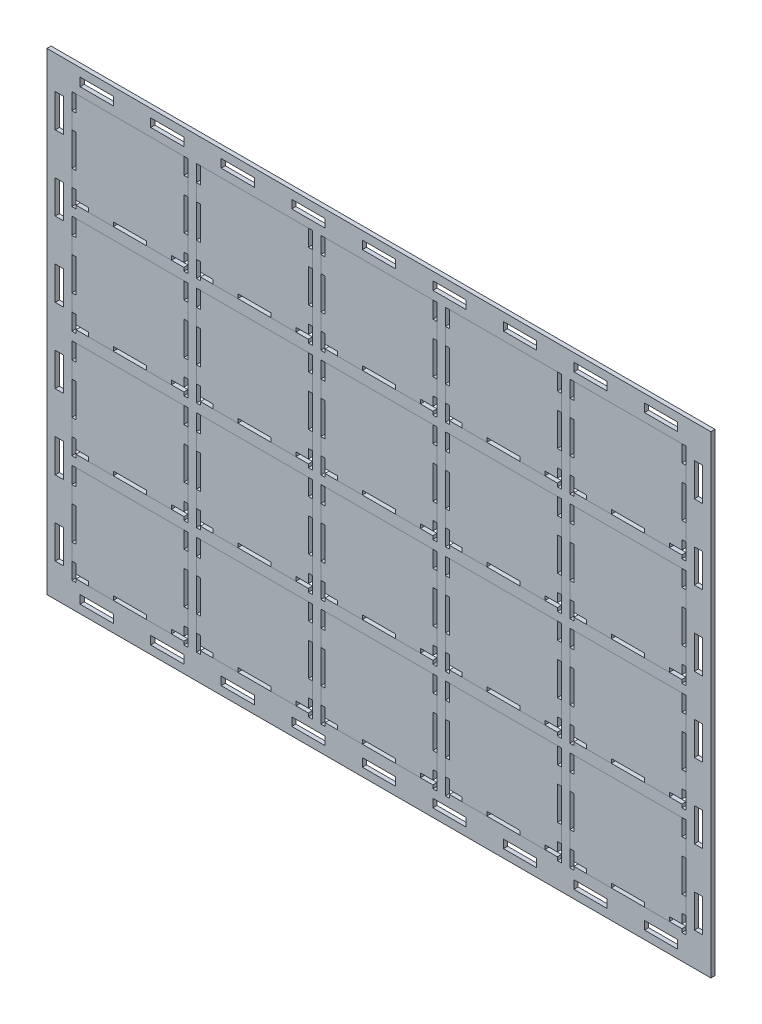
SolidWorks part; units mm, degrees
ref_plane "Front" through (0, 0, 0) normal (0, 0, 1) x (1, 0, 0)
ref_plane "Top" through (0, 0, 0) normal (0, 1, 0) x (1, 0, 0)
ref_plane "Right" through (0, 0, 0) normal (1, 0, 0) x (0, 0, -1)
sketch "Sketch1" plane through (0, 0, 0) normal (0, 0, 1) x (1, 0, 0)
  line L0 (-336.296, -110.6441) -> (-336.296, 164.3559) construction
  line L1 (-341.296, -115.6441) -> (58.704, -115.6441)
  line L2 (-341.296, -115.6441) -> (-341.296, 169.3559)
  line L3 (-341.296, 169.3559) -> (58.704, 169.3559)
  line L4 (58.704, -115.6441) -> (58.704, 169.3559)
  line L5 (-341.296, -115.6441) -> (58.704, 169.3559) construction
  line L6 (-341.296, 169.3559) -> (58.704, -115.6441) construction
  line L7 (-336.296, 164.3559) -> (53.704, 164.3559) construction
  line L8 (53.704, -110.6441) -> (53.704, 164.3559) construction
  line L9 (-336.296, -110.6441) -> (53.704, -110.6441) construction
  line L10 (-331.296, -105.6441) -> (-331.296, 159.3559) construction
  line L11 (-331.296, 159.3559) -> (48.704, 159.3559) construction
  line L12 (48.704, -105.6441) -> (48.704, 159.3559) construction
  line L13 (-331.296, -105.6441) -> (48.704, -105.6441) construction
  line L14 (-26.296, 96.3559) -> (43.704, 96.3559) construction
  line L15 (-26.296, 94.3559) -> (43.704, 94.3559) construction
  line L16 (-26.296, 94.3559) -> (-26.296, 154.3559) construction
  line L17 (-26.296, 154.3559) -> (43.704, 154.3559) construction
  line L18 (43.704, 94.3559) -> (43.704, 154.3559) construction
  line L19 (-26.296, 94.3559) -> (43.704, 154.3559) construction
  line L20 (-26.296, 154.3559) -> (43.704, 94.3559) construction
  line L21 (41.204, 154.3559) -> (41.204, 94.3559) construction
  line L22 (8.704, 134.2642) -> (8.704, 116.5512) construction
  line L23 (-23.796, 154.3559) -> (-23.796, 94.3559) construction
  line L24 (-26.296, 94.3559) -> (-26.296, 154.3559)
  line L25 (-26.296, 154.3559) -> (43.704, 154.3559)
  line L26 (43.704, 154.3559) -> (43.704, 94.3559)
  line L27 (43.704, 94.3559) -> (41.204, 94.3559)
  line L28 (41.204, 94.3559) -> (41.204, 96.3559)
  line L29 (-23.796, 94.3559) -> (-23.796, 96.3559)
  line L30 (-23.796, 96.3559) -> (41.204, 96.3559)
  line L31 (-23.796, 94.3559) -> (-26.296, 94.3559)
  line L32 (-23.796, 29.3559) -> (-26.296, 29.3559)
  line L33 (-26.296, 29.3559) -> (-26.296, 89.3559)
  line L34 (-26.296, 89.3559) -> (43.704, 89.3559)
  line L35 (43.704, 89.3559) -> (43.704, 29.3559)
  line L36 (43.704, 29.3559) -> (41.204, 29.3559)
  line L37 (41.204, 29.3559) -> (41.204, 31.3559)
  line L38 (-23.796, 31.3559) -> (41.204, 31.3559)
  line L39 (-23.796, 29.3559) -> (-23.796, 31.3559)
  line L40 (-23.796, -35.6441) -> (-26.296, -35.6441)
  line L41 (-26.296, -35.6441) -> (-26.296, 24.3559)
  line L42 (-26.296, 24.3559) -> (43.704, 24.3559)
  line L43 (43.704, 24.3559) -> (43.704, -35.6441)
  line L44 (43.704, -35.6441) -> (41.204, -35.6441)
  line L45 (41.204, -35.6441) -> (41.204, -33.6441)
  line L46 (-23.796, -33.6441) -> (41.204, -33.6441)
  line L47 (-23.796, -35.6441) -> (-23.796, -33.6441)
  line L48 (-23.796, -100.6441) -> (-26.296, -100.6441)
  line L49 (-26.296, -100.6441) -> (-26.296, -40.6441)
  line L50 (-26.296, -40.6441) -> (43.704, -40.6441)
  line L51 (43.704, -40.6441) -> (43.704, -100.6441)
  line L52 (43.704, -100.6441) -> (41.204, -100.6441)
  line L53 (41.204, -100.6441) -> (41.204, -98.6441)
  line L54 (-23.796, -98.6441) -> (41.204, -98.6441)
  line L55 (-23.796, -100.6441) -> (-23.796, -98.6441)
  line L56 (-98.796, 94.3559) -> (-101.296, 94.3559)
  line L57 (-101.296, 94.3559) -> (-101.296, 154.3559)
  line L58 (-101.296, 154.3559) -> (-31.296, 154.3559)
  line L59 (-31.296, 154.3559) -> (-31.296, 94.3559)
  line L60 (-31.296, 94.3559) -> (-33.796, 94.3559)
  line L61 (-33.796, 94.3559) -> (-33.796, 96.3559)
  line L62 (-98.796, 96.3559) -> (-33.796, 96.3559)
  line L63 (-98.796, 94.3559) -> (-98.796, 96.3559)
  line L64 (-98.796, 29.3559) -> (-101.296, 29.3559)
  line L65 (-101.296, 29.3559) -> (-101.296, 89.3559)
  line L66 (-101.296, 89.3559) -> (-31.296, 89.3559)
  line L67 (-31.296, 89.3559) -> (-31.296, 29.3559)
  line L68 (-31.296, 29.3559) -> (-33.796, 29.3559)
  line L69 (-33.796, 29.3559) -> (-33.796, 31.3559)
  line L70 (-98.796, 31.3559) -> (-33.796, 31.3559)
  line L71 (-98.796, 29.3559) -> (-98.796, 31.3559)
  line L72 (-98.796, -35.6441) -> (-101.296, -35.6441)
  line L73 (-101.296, -35.6441) -> (-101.296, 24.3559)
  line L74 (-101.296, 24.3559) -> (-31.296, 24.3559)
  line L75 (-31.296, 24.3559) -> (-31.296, -35.6441)
  line L76 (-31.296, -35.6441) -> (-33.796, -35.6441)
  line L77 (-33.796, -35.6441) -> (-33.796, -33.6441)
  line L78 (-98.796, -33.6441) -> (-33.796, -33.6441)
  line L79 (-98.796, -35.6441) -> (-98.796, -33.6441)
  line L80 (-98.796, -100.6441) -> (-101.296, -100.6441)
  line L81 (-101.296, -100.6441) -> (-101.296, -40.6441)
  line L82 (-101.296, -40.6441) -> (-31.296, -40.6441)
  line L83 (-31.296, -40.6441) -> (-31.296, -100.6441)
  line L84 (-31.296, -100.6441) -> (-33.796, -100.6441)
  line L85 (-33.796, -100.6441) -> (-33.796, -98.6441)
  line L86 (-98.796, -98.6441) -> (-33.796, -98.6441)
  line L87 (-98.796, -100.6441) -> (-98.796, -98.6441)
  line L88 (-173.796, 94.3559) -> (-176.296, 94.3559)
  line L89 (-176.296, 94.3559) -> (-176.296, 154.3559)
  line L90 (-176.296, 154.3559) -> (-106.296, 154.3559)
  line L91 (-106.296, 154.3559) -> (-106.296, 94.3559)
  line L92 (-106.296, 94.3559) -> (-108.796, 94.3559)
  line L93 (-108.796, 94.3559) -> (-108.796, 96.3559)
  line L94 (-173.796, 96.3559) -> (-108.796, 96.3559)
  line L95 (-173.796, 94.3559) -> (-173.796, 96.3559)
  line L96 (-173.796, 29.3559) -> (-176.296, 29.3559)
  line L97 (-176.296, 29.3559) -> (-176.296, 89.3559)
  line L98 (-176.296, 89.3559) -> (-106.296, 89.3559)
  line L99 (-106.296, 89.3559) -> (-106.296, 29.3559)
  line L100 (-106.296, 29.3559) -> (-108.796, 29.3559)
  line L101 (-108.796, 29.3559) -> (-108.796, 31.3559)
  line L102 (-173.796, 31.3559) -> (-108.796, 31.3559)
  line L103 (-173.796, 29.3559) -> (-173.796, 31.3559)
  line L104 (-173.796, -35.6441) -> (-176.296, -35.6441)
  line L105 (-176.296, -35.6441) -> (-176.296, 24.3559)
  line L106 (-176.296, 24.3559) -> (-106.296, 24.3559)
  line L107 (-106.296, 24.3559) -> (-106.296, -35.6441)
  line L108 (-106.296, -35.6441) -> (-108.796, -35.6441)
  line L109 (-108.796, -35.6441) -> (-108.796, -33.6441)
  line L110 (-173.796, -33.6441) -> (-108.796, -33.6441)
  line L111 (-173.796, -35.6441) -> (-173.796, -33.6441)
  line L112 (-173.796, -100.6441) -> (-176.296, -100.6441)
  line L113 (-176.296, -100.6441) -> (-176.296, -40.6441)
  line L114 (-176.296, -40.6441) -> (-106.296, -40.6441)
  line L115 (-106.296, -40.6441) -> (-106.296, -100.6441)
  line L116 (-106.296, -100.6441) -> (-108.796, -100.6441)
  line L117 (-108.796, -100.6441) -> (-108.796, -98.6441)
  line L118 (-173.796, -98.6441) -> (-108.796, -98.6441)
  line L119 (-173.796, -100.6441) -> (-173.796, -98.6441)
  line L120 (-248.796, 94.3559) -> (-251.296, 94.3559)
  line L121 (-251.296, 94.3559) -> (-251.296, 154.3559)
  line L122 (-251.296, 154.3559) -> (-181.296, 154.3559)
  line L123 (-181.296, 154.3559) -> (-181.296, 94.3559)
  line L124 (-181.296, 94.3559) -> (-183.796, 94.3559)
  line L125 (-183.796, 94.3559) -> (-183.796, 96.3559)
  line L126 (-248.796, 96.3559) -> (-183.796, 96.3559)
  line L127 (-248.796, 94.3559) -> (-248.796, 96.3559)
  line L128 (-248.796, 29.3559) -> (-251.296, 29.3559)
  line L129 (-251.296, 29.3559) -> (-251.296, 89.3559)
  line L130 (-251.296, 89.3559) -> (-181.296, 89.3559)
  line L131 (-181.296, 89.3559) -> (-181.296, 29.3559)
  line L132 (-181.296, 29.3559) -> (-183.796, 29.3559)
  line L133 (-183.796, 29.3559) -> (-183.796, 31.3559)
  line L134 (-248.796, 31.3559) -> (-183.796, 31.3559)
  line L135 (-248.796, 29.3559) -> (-248.796, 31.3559)
  line L136 (-248.796, -35.6441) -> (-251.296, -35.6441)
  line L137 (-251.296, -35.6441) -> (-251.296, 24.3559)
  line L138 (-251.296, 24.3559) -> (-181.296, 24.3559)
  line L139 (-181.296, 24.3559) -> (-181.296, -35.6441)
  line L140 (-181.296, -35.6441) -> (-183.796, -35.6441)
  line L141 (-183.796, -35.6441) -> (-183.796, -33.6441)
  line L142 (-248.796, -33.6441) -> (-183.796, -33.6441)
  line L143 (-248.796, -35.6441) -> (-248.796, -33.6441)
  line L144 (-248.796, -100.6441) -> (-251.296, -100.6441)
  line L145 (-251.296, -100.6441) -> (-251.296, -40.6441)
  line L146 (-251.296, -40.6441) -> (-181.296, -40.6441)
  line L147 (-181.296, -40.6441) -> (-181.296, -100.6441)
  line L148 (-181.296, -100.6441) -> (-183.796, -100.6441)
  line L149 (-183.796, -100.6441) -> (-183.796, -98.6441)
  line L150 (-248.796, -98.6441) -> (-183.796, -98.6441)
  line L151 (-248.796, -100.6441) -> (-248.796, -98.6441)
  line L152 (-323.796, 94.3559) -> (-326.296, 94.3559)
  line L153 (-326.296, 94.3559) -> (-326.296, 154.3559)
  line L154 (-326.296, 154.3559) -> (-256.296, 154.3559)
  line L155 (-256.296, 154.3559) -> (-256.296, 94.3559)
  line L156 (-256.296, 94.3559) -> (-258.796, 94.3559)
  line L157 (-258.796, 94.3559) -> (-258.796, 96.3559)
  line L158 (-323.796, 96.3559) -> (-258.796, 96.3559)
  line L159 (-323.796, 94.3559) -> (-323.796, 96.3559)
  line L160 (-323.796, 29.3559) -> (-326.296, 29.3559)
  line L161 (-326.296, 29.3559) -> (-326.296, 89.3559)
  line L162 (-326.296, 89.3559) -> (-256.296, 89.3559)
  line L163 (-256.296, 89.3559) -> (-256.296, 29.3559)
  line L164 (-256.296, 29.3559) -> (-258.796, 29.3559)
  line L165 (-258.796, 29.3559) -> (-258.796, 31.3559)
  line L166 (-323.796, 31.3559) -> (-258.796, 31.3559)
  line L167 (-323.796, 29.3559) -> (-323.796, 31.3559)
  line L168 (-323.796, -35.6441) -> (-326.296, -35.6441)
  line L169 (-326.296, -35.6441) -> (-326.296, 24.3559)
  line L170 (-326.296, 24.3559) -> (-256.296, 24.3559)
  line L171 (-256.296, 24.3559) -> (-256.296, -35.6441)
  line L172 (-256.296, -35.6441) -> (-258.796, -35.6441)
  line L173 (-258.796, -35.6441) -> (-258.796, -33.6441)
  line L174 (-323.796, -33.6441) -> (-258.796, -33.6441)
  line L175 (-323.796, -35.6441) -> (-323.796, -33.6441)
  line L176 (-323.796, -100.6441) -> (-326.296, -100.6441)
  line L177 (-326.296, -100.6441) -> (-326.296, -40.6441)
  line L178 (-326.296, -40.6441) -> (-256.296, -40.6441)
  line L179 (-256.296, -40.6441) -> (-256.296, -100.6441)
  line L180 (-256.296, -100.6441) -> (-258.796, -100.6441)
  line L181 (-258.796, -100.6441) -> (-258.796, -98.6441)
  line L182 (-323.796, -98.6441) -> (-258.796, -98.6441)
  line L183 (-323.796, -100.6441) -> (-323.796, -98.6441)
  line L184 (-119.2091, 26.8559) -> (-161.6715, 26.8559) construction
  line L185 (-321.296, 164.3559) -> (-301.296, 164.3559)
  line L186 (-321.296, 164.3559) -> (-321.296, 159.3559)
  line L187 (-321.296, 159.3559) -> (-301.296, 159.3559)
  line L188 (-301.296, 164.3559) -> (-301.296, 159.3559)
  line L189 (-321.296, 164.3559) -> (-301.296, 159.3559) construction
  line L190 (-321.296, 159.3559) -> (-301.296, 164.3559) construction
  line L191 (-141.296, 49.4928) -> (-141.296, 19.2296) construction
  line L192 (-321.296, -105.6441) -> (-301.296, -105.6441)
  line L193 (-301.296, -110.6441) -> (-301.296, -105.6441)
  line L194 (-321.296, -110.6441) -> (-301.296, -110.6441)
  line L195 (-321.296, -110.6441) -> (-321.296, -105.6441)
  line L196 (-278.796, 164.3559) -> (-278.796, 159.3559)
  line L197 (-278.796, 164.3559) -> (-258.796, 164.3559)
  line L198 (-258.796, 164.3559) -> (-258.796, 159.3559)
  line L199 (-278.796, 159.3559) -> (-258.796, 159.3559)
  line L200 (-278.796, -105.6441) -> (-258.796, -105.6441)
  line L201 (-258.796, -110.6441) -> (-258.796, -105.6441)
  line L202 (-278.796, -110.6441) -> (-258.796, -110.6441)
  line L203 (-278.796, -110.6441) -> (-278.796, -105.6441)
  line L204 (-236.296, 164.3559) -> (-236.296, 159.3559)
  line L205 (-236.296, 164.3559) -> (-216.296, 164.3559)
  line L206 (-216.296, 164.3559) -> (-216.296, 159.3559)
  line L207 (-236.296, 159.3559) -> (-216.296, 159.3559)
  line L208 (-236.296, -105.6441) -> (-216.296, -105.6441)
  line L209 (-216.296, -110.6441) -> (-216.296, -105.6441)
  line L210 (-236.296, -110.6441) -> (-216.296, -110.6441)
  line L211 (-236.296, -110.6441) -> (-236.296, -105.6441)
  line L212 (-193.796, 164.3559) -> (-193.796, 159.3559)
  line L213 (-193.796, 164.3559) -> (-173.796, 164.3559)
  line L214 (-173.796, 164.3559) -> (-173.796, 159.3559)
  line L215 (-193.796, 159.3559) -> (-173.796, 159.3559)
  line L216 (-193.796, -105.6441) -> (-173.796, -105.6441)
  line L217 (-173.796, -110.6441) -> (-173.796, -105.6441)
  line L218 (-193.796, -110.6441) -> (-173.796, -110.6441)
  line L219 (-193.796, -110.6441) -> (-193.796, -105.6441)
  line L220 (-151.296, 164.3559) -> (-151.296, 159.3559)
  line L221 (-151.296, 164.3559) -> (-131.296, 164.3559)
  line L222 (-131.296, 164.3559) -> (-131.296, 159.3559)
  line L223 (-151.296, 159.3559) -> (-131.296, 159.3559)
  line L224 (-151.296, -105.6441) -> (-131.296, -105.6441)
  line L225 (-131.296, -110.6441) -> (-131.296, -105.6441)
  line L226 (-151.296, -110.6441) -> (-131.296, -110.6441)
  line L227 (-151.296, -110.6441) -> (-151.296, -105.6441)
  line L228 (-108.796, 164.3559) -> (-108.796, 159.3559)
  line L229 (-108.796, 164.3559) -> (-88.796, 164.3559)
  line L230 (-88.796, 164.3559) -> (-88.796, 159.3559)
  line L231 (-108.796, 159.3559) -> (-88.796, 159.3559)
  line L232 (-108.796, -105.6441) -> (-88.796, -105.6441)
  line L233 (-88.796, -110.6441) -> (-88.796, -105.6441)
  line L234 (-108.796, -110.6441) -> (-88.796, -110.6441)
  line L235 (-108.796, -110.6441) -> (-108.796, -105.6441)
  line L236 (-66.296, 164.3559) -> (-66.296, 159.3559)
  line L237 (-66.296, 164.3559) -> (-46.296, 164.3559)
  line L238 (-46.296, 164.3559) -> (-46.296, 159.3559)
  line L239 (-66.296, 159.3559) -> (-46.296, 159.3559)
  line L240 (-66.296, -105.6441) -> (-46.296, -105.6441)
  line L241 (-46.296, -110.6441) -> (-46.296, -105.6441)
  line L242 (-66.296, -110.6441) -> (-46.296, -110.6441)
  line L243 (-66.296, -110.6441) -> (-66.296, -105.6441)
  line L244 (-23.796, 164.3559) -> (-23.796, 159.3559)
  line L245 (-23.796, 164.3559) -> (-3.796, 164.3559)
  line L246 (-3.796, 164.3559) -> (-3.796, 159.3559)
  line L247 (-23.796, 159.3559) -> (-3.796, 159.3559)
  line L248 (-23.796, -105.6441) -> (-3.796, -105.6441)
  line L249 (-3.796, -110.6441) -> (-3.796, -105.6441)
  line L250 (-23.796, -110.6441) -> (-3.796, -110.6441)
  line L251 (-23.796, -110.6441) -> (-23.796, -105.6441)
  line L252 (18.704, 164.3559) -> (18.704, 159.3559)
  line L253 (18.704, 164.3559) -> (38.704, 164.3559)
  line L254 (38.704, 164.3559) -> (38.704, 159.3559)
  line L255 (18.704, 159.3559) -> (38.704, 159.3559)
  line L256 (18.704, -105.6441) -> (38.704, -105.6441)
  line L257 (38.704, -110.6441) -> (38.704, -105.6441)
  line L258 (18.704, -110.6441) -> (38.704, -110.6441)
  line L259 (18.704, -110.6441) -> (18.704, -105.6441)
  line L260 (48.704, 129.3559) -> (53.704, 129.3559)
  line L261 (-331.296, 149.3559) -> (-336.296, 149.3559)
  line L262 (-331.296, 149.3559) -> (-331.296, 129.3559)
  line L263 (-331.296, 129.3559) -> (-336.296, 129.3559)
  line L264 (-336.296, 149.3559) -> (-336.296, 129.3559)
  line L265 (-331.296, 149.3559) -> (-336.296, 129.3559) construction
  line L266 (-331.296, 129.3559) -> (-336.296, 149.3559) construction
  line L267 (53.704, 149.3559) -> (53.704, 129.3559)
  line L268 (48.704, 149.3559) -> (53.704, 149.3559)
  line L269 (48.704, 149.3559) -> (48.704, 129.3559)
  line L270 (-331.296, 104.3559) -> (-331.296, 84.3559)
  line L271 (-331.296, 104.3559) -> (-336.296, 104.3559)
  line L272 (-336.296, 104.3559) -> (-336.296, 84.3559)
  line L273 (-331.296, 84.3559) -> (-336.296, 84.3559)
  line L274 (48.704, 84.3559) -> (53.704, 84.3559)
  line L275 (53.704, 104.3559) -> (53.704, 84.3559)
  line L276 (48.704, 104.3559) -> (53.704, 104.3559)
  line L277 (48.704, 104.3559) -> (48.704, 84.3559)
  line L278 (-331.296, 59.3559) -> (-331.296, 39.3559)
  line L279 (-331.296, 59.3559) -> (-336.296, 59.3559)
  line L280 (-336.296, 59.3559) -> (-336.296, 39.3559)
  line L281 (-331.296, 39.3559) -> (-336.296, 39.3559)
  line L282 (48.704, 39.3559) -> (53.704, 39.3559)
  line L283 (53.704, 59.3559) -> (53.704, 39.3559)
  line L284 (48.704, 59.3559) -> (53.704, 59.3559)
  line L285 (48.704, 59.3559) -> (48.704, 39.3559)
  line L286 (-331.296, 14.3559) -> (-331.296, -5.6441)
  line L287 (-331.296, 14.3559) -> (-336.296, 14.3559)
  line L288 (-336.296, 14.3559) -> (-336.296, -5.6441)
  line L289 (-331.296, -5.6441) -> (-336.296, -5.6441)
  line L290 (48.704, -5.6441) -> (53.704, -5.6441)
  line L291 (53.704, 14.3559) -> (53.704, -5.6441)
  line L292 (48.704, 14.3559) -> (53.704, 14.3559)
  line L293 (48.704, 14.3559) -> (48.704, -5.6441)
  line L294 (-331.296, -30.6441) -> (-331.296, -50.6441)
  line L295 (-331.296, -30.6441) -> (-336.296, -30.6441)
  line L296 (-336.296, -30.6441) -> (-336.296, -50.6441)
  line L297 (-331.296, -50.6441) -> (-336.296, -50.6441)
  line L298 (48.704, -50.6441) -> (53.704, -50.6441)
  line L299 (53.704, -30.6441) -> (53.704, -50.6441)
  line L300 (48.704, -30.6441) -> (53.704, -30.6441)
  line L301 (48.704, -30.6441) -> (48.704, -50.6441)
  line L302 (-331.296, -75.6441) -> (-331.296, -95.6441)
  line L303 (-331.296, -75.6441) -> (-336.296, -75.6441)
  line L304 (-336.296, -75.6441) -> (-336.296, -95.6441)
  line L305 (-331.296, -95.6441) -> (-336.296, -95.6441)
  line L306 (48.704, -95.6441) -> (53.704, -95.6441)
  line L307 (53.704, -75.6441) -> (53.704, -95.6441)
  line L308 (48.704, -75.6441) -> (53.704, -75.6441)
  line L309 (48.704, -75.6441) -> (48.704, -95.6441)
  line L310 (-26.296, 98.8559) -> (43.704, 98.8559) construction
  line L311 (-26.296, 94.3559) -> (43.704, 94.3559) construction
  line L312 (-26.296, 94.3559) -> (-26.296, 154.3559) construction
  line L313 (-26.296, 154.3559) -> (43.704, 154.3559) construction
  line L314 (43.704, 94.3559) -> (43.704, 154.3559) construction
  line L315 (-26.296, 94.3559) -> (43.704, 154.3559) construction
  line L316 (-26.296, 154.3559) -> (43.704, 94.3559) construction
  line L317 (8.704, 132.327) -> (8.704, 114.7588) construction
  line L318 (-16.296, 124.3559) -> (33.704, 124.3559) construction
  line L319 (-23.796, 154.3559) -> (-23.796, 94.3559) construction
  line L320 (41.204, 154.3559) -> (41.204, 94.3559) construction
  line L321 (33.704, 96.3559) -> (18.704, 96.3559)
  line L322 (-16.296, 98.8559) -> (-1.296, 98.8559) construction
  line L323 (-16.296, 98.8559) -> (-16.296, 96.3559)
  line L324 (-16.296, 96.3559) -> (-1.296, 96.3559)
  line L325 (-1.296, 98.8559) -> (-1.296, 96.3559)
  line L326 (-16.296, 98.8559) -> (-1.296, 96.3559) construction
  line L327 (-16.296, 96.3559) -> (-1.296, 98.8559) construction
  line L328 (18.704, 98.8559) -> (18.704, 96.3559)
  line L329 (33.704, 98.8559) -> (18.704, 98.8559) construction
  line L330 (33.704, 98.8559) -> (33.704, 96.3559)
  line L331 (-23.796, 114.3559) -> (-23.796, 134.3559)
  line L332 (-23.796, 134.3559) -> (-26.296, 134.3559)
  line L333 (-26.296, 134.3559) -> (-26.296, 144.3559)
  line L334 (-26.296, 144.3559) -> (-23.796, 144.3559)
  line L335 (-23.796, 144.3559) -> (-23.796, 154.3559) construction
  line L336 (-23.796, 154.3559) -> (41.204, 154.3559) construction
  line L337 (41.204, 144.3559) -> (41.204, 154.3559) construction
  line L338 (43.704, 144.3559) -> (41.204, 144.3559)
  line L339 (43.704, 134.3559) -> (43.704, 144.3559)
  line L340 (41.204, 134.3559) -> (43.704, 134.3559)
  line L341 (41.204, 114.3559) -> (41.204, 134.3559)
  line L342 (41.204, 114.3559) -> (43.704, 114.3559)
  line L343 (43.704, 114.3559) -> (43.704, 104.3559)
  line L344 (43.704, 104.3559) -> (41.204, 104.3559)
  line L345 (-23.796, 104.3559) -> (-23.796, 98.8559)
  line L346 (-23.796, 98.8559) -> (-16.296, 98.8559)
  line L347 (-26.296, 104.3559) -> (-23.796, 104.3559)
  line L348 (-26.296, 114.3559) -> (-26.296, 104.3559)
  line L349 (-23.796, 114.3559) -> (-26.296, 114.3559)
  line L350 (-23.796, 154.3559) -> (41.204, 154.3559)
  line L351 (-23.796, 154.3559) -> (-23.796, 144.3559)
  line L352 (41.204, 154.3559) -> (41.204, 144.3559)
  line L353 (-1.296, 98.8559) -> (18.704, 98.8559)
  line L354 (33.704, 98.8559) -> (41.204, 98.8559)
  line L355 (41.204, 98.8559) -> (41.204, 104.3559)
  line L356 (-1.296, 33.8559) -> (18.704, 33.8559)
  line L357 (18.704, 33.8559) -> (18.704, 31.3559)
  line L358 (33.704, 31.3559) -> (18.704, 31.3559)
  line L359 (33.704, 33.8559) -> (33.704, 31.3559)
  line L360 (33.704, 33.8559) -> (41.204, 33.8559)
  line L361 (41.204, 33.8559) -> (41.204, 39.3559)
  line L362 (43.704, 39.3559) -> (41.204, 39.3559)
  line L363 (43.704, 49.3559) -> (43.704, 39.3559)
  line L364 (41.204, 49.3559) -> (43.704, 49.3559)
  line L365 (41.204, 49.3559) -> (41.204, 69.3559)
  line L366 (41.204, 69.3559) -> (43.704, 69.3559)
  line L367 (43.704, 69.3559) -> (43.704, 79.3559)
  line L368 (43.704, 79.3559) -> (41.204, 79.3559)
  line L369 (41.204, 89.3559) -> (41.204, 79.3559)
  line L370 (-23.796, 89.3559) -> (41.204, 89.3559)
  line L371 (-23.796, 89.3559) -> (-23.796, 79.3559)
  line L372 (-26.296, 79.3559) -> (-23.796, 79.3559)
  line L373 (-26.296, 69.3559) -> (-26.296, 79.3559)
  line L374 (-23.796, 69.3559) -> (-26.296, 69.3559)
  line L375 (-23.796, 49.3559) -> (-23.796, 69.3559)
  line L376 (-23.796, 49.3559) -> (-26.296, 49.3559)
  line L377 (-26.296, 49.3559) -> (-26.296, 39.3559)
  line L378 (-26.296, 39.3559) -> (-23.796, 39.3559)
  line L379 (-23.796, 39.3559) -> (-23.796, 33.8559)
  line L380 (-23.796, 33.8559) -> (-16.296, 33.8559)
  line L381 (-16.296, 33.8559) -> (-16.296, 31.3559)
  line L382 (-16.296, 31.3559) -> (-1.296, 31.3559)
  line L383 (-1.296, 33.8559) -> (-1.296, 31.3559)
  line L384 (-1.296, -31.1441) -> (18.704, -31.1441)
  line L385 (18.704, -31.1441) -> (18.704, -33.6441)
  line L386 (33.704, -33.6441) -> (18.704, -33.6441)
  line L387 (33.704, -31.1441) -> (33.704, -33.6441)
  line L388 (33.704, -31.1441) -> (41.204, -31.1441)
  line L389 (41.204, -31.1441) -> (41.204, -25.6441)
  line L390 (43.704, -25.6441) -> (41.204, -25.6441)
  line L391 (43.704, -15.6441) -> (43.704, -25.6441)
  line L392 (41.204, -15.6441) -> (43.704, -15.6441)
  line L393 (41.204, -15.6441) -> (41.204, 4.3559)
  line L394 (41.204, 4.3559) -> (43.704, 4.3559)
  line L395 (43.704, 4.3559) -> (43.704, 14.3559)
  line L396 (43.704, 14.3559) -> (41.204, 14.3559)
  line L397 (41.204, 24.3559) -> (41.204, 14.3559)
  line L398 (-23.796, 24.3559) -> (41.204, 24.3559)
  line L399 (-23.796, 24.3559) -> (-23.796, 14.3559)
  line L400 (-26.296, 14.3559) -> (-23.796, 14.3559)
  line L401 (-26.296, 4.3559) -> (-26.296, 14.3559)
  line L402 (-23.796, 4.3559) -> (-26.296, 4.3559)
  line L403 (-23.796, -15.6441) -> (-23.796, 4.3559)
  line L404 (-23.796, -15.6441) -> (-26.296, -15.6441)
  line L405 (-26.296, -15.6441) -> (-26.296, -25.6441)
  line L406 (-26.296, -25.6441) -> (-23.796, -25.6441)
  line L407 (-23.796, -25.6441) -> (-23.796, -31.1441)
  line L408 (-23.796, -31.1441) -> (-16.296, -31.1441)
  line L409 (-16.296, -31.1441) -> (-16.296, -33.6441)
  line L410 (-16.296, -33.6441) -> (-1.296, -33.6441)
  line L411 (-1.296, -31.1441) -> (-1.296, -33.6441)
  line L412 (-1.296, -96.1441) -> (18.704, -96.1441)
  line L413 (18.704, -96.1441) -> (18.704, -98.6441)
  line L414 (33.704, -98.6441) -> (18.704, -98.6441)
  line L415 (33.704, -96.1441) -> (33.704, -98.6441)
  line L416 (33.704, -96.1441) -> (41.204, -96.1441)
  line L417 (41.204, -96.1441) -> (41.204, -90.6441)
  line L418 (43.704, -90.6441) -> (41.204, -90.6441)
  line L419 (43.704, -80.6441) -> (43.704, -90.6441)
  line L420 (41.204, -80.6441) -> (43.704, -80.6441)
  line L421 (41.204, -80.6441) -> (41.204, -60.6441)
  line L422 (41.204, -60.6441) -> (43.704, -60.6441)
  line L423 (43.704, -60.6441) -> (43.704, -50.6441)
  line L424 (43.704, -50.6441) -> (41.204, -50.6441)
  line L425 (41.204, -40.6441) -> (41.204, -50.6441)
  line L426 (-23.796, -40.6441) -> (41.204, -40.6441)
  line L427 (-23.796, -40.6441) -> (-23.796, -50.6441)
  line L428 (-26.296, -50.6441) -> (-23.796, -50.6441)
  line L429 (-26.296, -60.6441) -> (-26.296, -50.6441)
  line L430 (-23.796, -60.6441) -> (-26.296, -60.6441)
  line L431 (-23.796, -80.6441) -> (-23.796, -60.6441)
  line L432 (-23.796, -80.6441) -> (-26.296, -80.6441)
  line L433 (-26.296, -80.6441) -> (-26.296, -90.6441)
  line L434 (-26.296, -90.6441) -> (-23.796, -90.6441)
  line L435 (-23.796, -90.6441) -> (-23.796, -96.1441)
  line L436 (-23.796, -96.1441) -> (-16.296, -96.1441)
  line L437 (-16.296, -96.1441) -> (-16.296, -98.6441)
  line L438 (-16.296, -98.6441) -> (-1.296, -98.6441)
  line L439 (-1.296, -96.1441) -> (-1.296, -98.6441)
  line L440 (-76.296, 98.8559) -> (-56.296, 98.8559)
  line L441 (-56.296, 98.8559) -> (-56.296, 96.3559)
  line L442 (-41.296, 96.3559) -> (-56.296, 96.3559)
  line L443 (-41.296, 98.8559) -> (-41.296, 96.3559)
  line L444 (-41.296, 98.8559) -> (-33.796, 98.8559)
  line L445 (-33.796, 98.8559) -> (-33.796, 104.3559)
  line L446 (-31.296, 104.3559) -> (-33.796, 104.3559)
  line L447 (-31.296, 114.3559) -> (-31.296, 104.3559)
  line L448 (-33.796, 114.3559) -> (-31.296, 114.3559)
  line L449 (-33.796, 114.3559) -> (-33.796, 134.3559)
  line L450 (-33.796, 134.3559) -> (-31.296, 134.3559)
  line L451 (-31.296, 134.3559) -> (-31.296, 144.3559)
  line L452 (-31.296, 144.3559) -> (-33.796, 144.3559)
  line L453 (-33.796, 154.3559) -> (-33.796, 144.3559)
  line L454 (-98.796, 154.3559) -> (-33.796, 154.3559)
  line L455 (-98.796, 154.3559) -> (-98.796, 144.3559)
  line L456 (-101.296, 144.3559) -> (-98.796, 144.3559)
  line L457 (-101.296, 134.3559) -> (-101.296, 144.3559)
  line L458 (-98.796, 134.3559) -> (-101.296, 134.3559)
  line L459 (-98.796, 114.3559) -> (-98.796, 134.3559)
  line L460 (-98.796, 114.3559) -> (-101.296, 114.3559)
  line L461 (-101.296, 114.3559) -> (-101.296, 104.3559)
  line L462 (-101.296, 104.3559) -> (-98.796, 104.3559)
  line L463 (-98.796, 104.3559) -> (-98.796, 98.8559)
  line L464 (-98.796, 98.8559) -> (-91.296, 98.8559)
  line L465 (-91.296, 98.8559) -> (-91.296, 96.3559)
  line L466 (-91.296, 96.3559) -> (-76.296, 96.3559)
  line L467 (-76.296, 98.8559) -> (-76.296, 96.3559)
  line L468 (-76.296, 33.8559) -> (-56.296, 33.8559)
  line L469 (-56.296, 33.8559) -> (-56.296, 31.3559)
  line L470 (-41.296, 31.3559) -> (-56.296, 31.3559)
  line L471 (-41.296, 33.8559) -> (-41.296, 31.3559)
  line L472 (-41.296, 33.8559) -> (-33.796, 33.8559)
  line L473 (-33.796, 33.8559) -> (-33.796, 39.3559)
  line L474 (-31.296, 39.3559) -> (-33.796, 39.3559)
  line L475 (-31.296, 49.3559) -> (-31.296, 39.3559)
  line L476 (-33.796, 49.3559) -> (-31.296, 49.3559)
  line L477 (-33.796, 49.3559) -> (-33.796, 69.3559)
  line L478 (-33.796, 69.3559) -> (-31.296, 69.3559)
  line L479 (-31.296, 69.3559) -> (-31.296, 79.3559)
  line L480 (-31.296, 79.3559) -> (-33.796, 79.3559)
  line L481 (-33.796, 89.3559) -> (-33.796, 79.3559)
  line L482 (-98.796, 89.3559) -> (-33.796, 89.3559)
  line L483 (-98.796, 89.3559) -> (-98.796, 79.3559)
  line L484 (-101.296, 79.3559) -> (-98.796, 79.3559)
  line L485 (-101.296, 69.3559) -> (-101.296, 79.3559)
  line L486 (-98.796, 69.3559) -> (-101.296, 69.3559)
  line L487 (-98.796, 49.3559) -> (-98.796, 69.3559)
  line L488 (-98.796, 49.3559) -> (-101.296, 49.3559)
  line L489 (-101.296, 49.3559) -> (-101.296, 39.3559)
  line L490 (-101.296, 39.3559) -> (-98.796, 39.3559)
  line L491 (-98.796, 39.3559) -> (-98.796, 33.8559)
  line L492 (-98.796, 33.8559) -> (-91.296, 33.8559)
  line L493 (-91.296, 33.8559) -> (-91.296, 31.3559)
  line L494 (-91.296, 31.3559) -> (-76.296, 31.3559)
  line L495 (-76.296, 33.8559) -> (-76.296, 31.3559)
  line L496 (-76.296, -31.1441) -> (-56.296, -31.1441)
  line L497 (-56.296, -31.1441) -> (-56.296, -33.6441)
  line L498 (-41.296, -33.6441) -> (-56.296, -33.6441)
  line L499 (-41.296, -31.1441) -> (-41.296, -33.6441)
  line L500 (-41.296, -31.1441) -> (-33.796, -31.1441)
  line L501 (-33.796, -31.1441) -> (-33.796, -25.6441)
  line L502 (-31.296, -25.6441) -> (-33.796, -25.6441)
  line L503 (-31.296, -15.6441) -> (-31.296, -25.6441)
  line L504 (-33.796, -15.6441) -> (-31.296, -15.6441)
  line L505 (-33.796, -15.6441) -> (-33.796, 4.3559)
  line L506 (-33.796, 4.3559) -> (-31.296, 4.3559)
  line L507 (-31.296, 4.3559) -> (-31.296, 14.3559)
  line L508 (-31.296, 14.3559) -> (-33.796, 14.3559)
  line L509 (-33.796, 24.3559) -> (-33.796, 14.3559)
  line L510 (-98.796, 24.3559) -> (-33.796, 24.3559)
  line L511 (-98.796, 24.3559) -> (-98.796, 14.3559)
  line L512 (-101.296, 14.3559) -> (-98.796, 14.3559)
  line L513 (-101.296, 4.3559) -> (-101.296, 14.3559)
  line L514 (-98.796, 4.3559) -> (-101.296, 4.3559)
  line L515 (-98.796, -15.6441) -> (-98.796, 4.3559)
  line L516 (-98.796, -15.6441) -> (-101.296, -15.6441)
  line L517 (-101.296, -15.6441) -> (-101.296, -25.6441)
  line L518 (-101.296, -25.6441) -> (-98.796, -25.6441)
  line L519 (-98.796, -25.6441) -> (-98.796, -31.1441)
  line L520 (-98.796, -31.1441) -> (-91.296, -31.1441)
  line L521 (-91.296, -31.1441) -> (-91.296, -33.6441)
  line L522 (-91.296, -33.6441) -> (-76.296, -33.6441)
  line L523 (-76.296, -31.1441) -> (-76.296, -33.6441)
  line L524 (-76.296, -96.1441) -> (-56.296, -96.1441)
  line L525 (-56.296, -96.1441) -> (-56.296, -98.6441)
  line L526 (-41.296, -98.6441) -> (-56.296, -98.6441)
  line L527 (-41.296, -96.1441) -> (-41.296, -98.6441)
  line L528 (-41.296, -96.1441) -> (-33.796, -96.1441)
  line L529 (-33.796, -96.1441) -> (-33.796, -90.6441)
  line L530 (-31.296, -90.6441) -> (-33.796, -90.6441)
  line L531 (-31.296, -80.6441) -> (-31.296, -90.6441)
  line L532 (-33.796, -80.6441) -> (-31.296, -80.6441)
  line L533 (-33.796, -80.6441) -> (-33.796, -60.6441)
  line L534 (-33.796, -60.6441) -> (-31.296, -60.6441)
  line L535 (-31.296, -60.6441) -> (-31.296, -50.6441)
  line L536 (-31.296, -50.6441) -> (-33.796, -50.6441)
  line L537 (-33.796, -40.6441) -> (-33.796, -50.6441)
  line L538 (-98.796, -40.6441) -> (-33.796, -40.6441)
  line L539 (-98.796, -40.6441) -> (-98.796, -50.6441)
  line L540 (-101.296, -50.6441) -> (-98.796, -50.6441)
  line L541 (-101.296, -60.6441) -> (-101.296, -50.6441)
  line L542 (-98.796, -60.6441) -> (-101.296, -60.6441)
  line L543 (-98.796, -80.6441) -> (-98.796, -60.6441)
  line L544 (-98.796, -80.6441) -> (-101.296, -80.6441)
  line L545 (-101.296, -80.6441) -> (-101.296, -90.6441)
  line L546 (-101.296, -90.6441) -> (-98.796, -90.6441)
  line L547 (-98.796, -90.6441) -> (-98.796, -96.1441)
  line L548 (-98.796, -96.1441) -> (-91.296, -96.1441)
  line L549 (-91.296, -96.1441) -> (-91.296, -98.6441)
  line L550 (-91.296, -98.6441) -> (-76.296, -98.6441)
  line L551 (-76.296, -96.1441) -> (-76.296, -98.6441)
  line L552 (-151.296, 98.8559) -> (-131.296, 98.8559)
  line L553 (-131.296, 98.8559) -> (-131.296, 96.3559)
  line L554 (-116.296, 96.3559) -> (-131.296, 96.3559)
  line L555 (-116.296, 98.8559) -> (-116.296, 96.3559)
  line L556 (-116.296, 98.8559) -> (-108.796, 98.8559)
  line L557 (-108.796, 98.8559) -> (-108.796, 104.3559)
  line L558 (-106.296, 104.3559) -> (-108.796, 104.3559)
  line L559 (-106.296, 114.3559) -> (-106.296, 104.3559)
  line L560 (-108.796, 114.3559) -> (-106.296, 114.3559)
  line L561 (-108.796, 114.3559) -> (-108.796, 134.3559)
  line L562 (-108.796, 134.3559) -> (-106.296, 134.3559)
  line L563 (-106.296, 134.3559) -> (-106.296, 144.3559)
  line L564 (-106.296, 144.3559) -> (-108.796, 144.3559)
  line L565 (-108.796, 154.3559) -> (-108.796, 144.3559)
  line L566 (-173.796, 154.3559) -> (-108.796, 154.3559)
  line L567 (-173.796, 154.3559) -> (-173.796, 144.3559)
  line L568 (-176.296, 144.3559) -> (-173.796, 144.3559)
  line L569 (-176.296, 134.3559) -> (-176.296, 144.3559)
  line L570 (-173.796, 134.3559) -> (-176.296, 134.3559)
  line L571 (-173.796, 114.3559) -> (-173.796, 134.3559)
  line L572 (-173.796, 114.3559) -> (-176.296, 114.3559)
  line L573 (-176.296, 114.3559) -> (-176.296, 104.3559)
  line L574 (-176.296, 104.3559) -> (-173.796, 104.3559)
  line L575 (-173.796, 104.3559) -> (-173.796, 98.8559)
  line L576 (-173.796, 98.8559) -> (-166.296, 98.8559)
  line L577 (-166.296, 98.8559) -> (-166.296, 96.3559)
  line L578 (-166.296, 96.3559) -> (-151.296, 96.3559)
  line L579 (-151.296, 98.8559) -> (-151.296, 96.3559)
  line L580 (-151.296, 33.8559) -> (-131.296, 33.8559)
  line L581 (-131.296, 33.8559) -> (-131.296, 31.3559)
  line L582 (-116.296, 31.3559) -> (-131.296, 31.3559)
  line L583 (-116.296, 33.8559) -> (-116.296, 31.3559)
  line L584 (-116.296, 33.8559) -> (-108.796, 33.8559)
  line L585 (-108.796, 33.8559) -> (-108.796, 39.3559)
  line L586 (-106.296, 39.3559) -> (-108.796, 39.3559)
  line L587 (-106.296, 49.3559) -> (-106.296, 39.3559)
  line L588 (-108.796, 49.3559) -> (-106.296, 49.3559)
  line L589 (-108.796, 49.3559) -> (-108.796, 69.3559)
  line L590 (-108.796, 69.3559) -> (-106.296, 69.3559)
  line L591 (-106.296, 69.3559) -> (-106.296, 79.3559)
  line L592 (-106.296, 79.3559) -> (-108.796, 79.3559)
  line L593 (-108.796, 89.3559) -> (-108.796, 79.3559)
  line L594 (-173.796, 89.3559) -> (-108.796, 89.3559)
  line L595 (-173.796, 89.3559) -> (-173.796, 79.3559)
  line L596 (-176.296, 79.3559) -> (-173.796, 79.3559)
  line L597 (-176.296, 69.3559) -> (-176.296, 79.3559)
  line L598 (-173.796, 69.3559) -> (-176.296, 69.3559)
  line L599 (-173.796, 49.3559) -> (-173.796, 69.3559)
  line L600 (-173.796, 49.3559) -> (-176.296, 49.3559)
  line L601 (-176.296, 49.3559) -> (-176.296, 39.3559)
  line L602 (-176.296, 39.3559) -> (-173.796, 39.3559)
  line L603 (-173.796, 39.3559) -> (-173.796, 33.8559)
  line L604 (-173.796, 33.8559) -> (-166.296, 33.8559)
  line L605 (-166.296, 33.8559) -> (-166.296, 31.3559)
  line L606 (-166.296, 31.3559) -> (-151.296, 31.3559)
  line L607 (-151.296, 33.8559) -> (-151.296, 31.3559)
  line L608 (-151.296, -31.1441) -> (-131.296, -31.1441)
  line L609 (-131.296, -31.1441) -> (-131.296, -33.6441)
  line L610 (-116.296, -33.6441) -> (-131.296, -33.6441)
  line L611 (-116.296, -31.1441) -> (-116.296, -33.6441)
  line L612 (-116.296, -31.1441) -> (-108.796, -31.1441)
  line L613 (-108.796, -31.1441) -> (-108.796, -25.6441)
  line L614 (-106.296, -25.6441) -> (-108.796, -25.6441)
  line L615 (-106.296, -15.6441) -> (-106.296, -25.6441)
  line L616 (-108.796, -15.6441) -> (-106.296, -15.6441)
  line L617 (-108.796, -15.6441) -> (-108.796, 4.3559)
  line L618 (-108.796, 4.3559) -> (-106.296, 4.3559)
  line L619 (-106.296, 4.3559) -> (-106.296, 14.3559)
  line L620 (-106.296, 14.3559) -> (-108.796, 14.3559)
  line L621 (-108.796, 24.3559) -> (-108.796, 14.3559)
  line L622 (-173.796, 24.3559) -> (-108.796, 24.3559)
  line L623 (-173.796, 24.3559) -> (-173.796, 14.3559)
  line L624 (-176.296, 14.3559) -> (-173.796, 14.3559)
  line L625 (-176.296, 4.3559) -> (-176.296, 14.3559)
  line L626 (-173.796, 4.3559) -> (-176.296, 4.3559)
  line L627 (-173.796, -15.6441) -> (-173.796, 4.3559)
  line L628 (-173.796, -15.6441) -> (-176.296, -15.6441)
  line L629 (-176.296, -15.6441) -> (-176.296, -25.6441)
  line L630 (-176.296, -25.6441) -> (-173.796, -25.6441)
  line L631 (-173.796, -25.6441) -> (-173.796, -31.1441)
  line L632 (-173.796, -31.1441) -> (-166.296, -31.1441)
  line L633 (-166.296, -31.1441) -> (-166.296, -33.6441)
  line L634 (-166.296, -33.6441) -> (-151.296, -33.6441)
  line L635 (-151.296, -31.1441) -> (-151.296, -33.6441)
  line L636 (-151.296, -96.1441) -> (-131.296, -96.1441)
  line L637 (-131.296, -96.1441) -> (-131.296, -98.6441)
  line L638 (-116.296, -98.6441) -> (-131.296, -98.6441)
  line L639 (-116.296, -96.1441) -> (-116.296, -98.6441)
  line L640 (-116.296, -96.1441) -> (-108.796, -96.1441)
  line L641 (-108.796, -96.1441) -> (-108.796, -90.6441)
  line L642 (-106.296, -90.6441) -> (-108.796, -90.6441)
  line L643 (-106.296, -80.6441) -> (-106.296, -90.6441)
  line L644 (-108.796, -80.6441) -> (-106.296, -80.6441)
  line L645 (-108.796, -80.6441) -> (-108.796, -60.6441)
  line L646 (-108.796, -60.6441) -> (-106.296, -60.6441)
  line L647 (-106.296, -60.6441) -> (-106.296, -50.6441)
  line L648 (-106.296, -50.6441) -> (-108.796, -50.6441)
  line L649 (-108.796, -40.6441) -> (-108.796, -50.6441)
  line L650 (-173.796, -40.6441) -> (-108.796, -40.6441)
  line L651 (-173.796, -40.6441) -> (-173.796, -50.6441)
  line L652 (-176.296, -50.6441) -> (-173.796, -50.6441)
  line L653 (-176.296, -60.6441) -> (-176.296, -50.6441)
  line L654 (-173.796, -60.6441) -> (-176.296, -60.6441)
  line L655 (-173.796, -80.6441) -> (-173.796, -60.6441)
  line L656 (-173.796, -80.6441) -> (-176.296, -80.6441)
  line L657 (-176.296, -80.6441) -> (-176.296, -90.6441)
  line L658 (-176.296, -90.6441) -> (-173.796, -90.6441)
  line L659 (-173.796, -90.6441) -> (-173.796, -96.1441)
  line L660 (-173.796, -96.1441) -> (-166.296, -96.1441)
  line L661 (-166.296, -96.1441) -> (-166.296, -98.6441)
  line L662 (-166.296, -98.6441) -> (-151.296, -98.6441)
  line L663 (-151.296, -96.1441) -> (-151.296, -98.6441)
  line L664 (-226.296, 98.8559) -> (-206.296, 98.8559)
  line L665 (-206.296, 98.8559) -> (-206.296, 96.3559)
  line L666 (-191.296, 96.3559) -> (-206.296, 96.3559)
  line L667 (-191.296, 98.8559) -> (-191.296, 96.3559)
  line L668 (-191.296, 98.8559) -> (-183.796, 98.8559)
  line L669 (-183.796, 98.8559) -> (-183.796, 104.3559)
  line L670 (-181.296, 104.3559) -> (-183.796, 104.3559)
  line L671 (-181.296, 114.3559) -> (-181.296, 104.3559)
  line L672 (-183.796, 114.3559) -> (-181.296, 114.3559)
  line L673 (-183.796, 114.3559) -> (-183.796, 134.3559)
  line L674 (-183.796, 134.3559) -> (-181.296, 134.3559)
  line L675 (-181.296, 134.3559) -> (-181.296, 144.3559)
  line L676 (-181.296, 144.3559) -> (-183.796, 144.3559)
  line L677 (-183.796, 154.3559) -> (-183.796, 144.3559)
  line L678 (-248.796, 154.3559) -> (-183.796, 154.3559)
  line L679 (-248.796, 154.3559) -> (-248.796, 144.3559)
  line L680 (-251.296, 144.3559) -> (-248.796, 144.3559)
  line L681 (-251.296, 134.3559) -> (-251.296, 144.3559)
  line L682 (-248.796, 134.3559) -> (-251.296, 134.3559)
  line L683 (-248.796, 114.3559) -> (-248.796, 134.3559)
  line L684 (-248.796, 114.3559) -> (-251.296, 114.3559)
  line L685 (-251.296, 114.3559) -> (-251.296, 104.3559)
  line L686 (-251.296, 104.3559) -> (-248.796, 104.3559)
  line L687 (-248.796, 104.3559) -> (-248.796, 98.8559)
  line L688 (-248.796, 98.8559) -> (-241.296, 98.8559)
  line L689 (-241.296, 98.8559) -> (-241.296, 96.3559)
  line L690 (-241.296, 96.3559) -> (-226.296, 96.3559)
  line L691 (-226.296, 98.8559) -> (-226.296, 96.3559)
  line L692 (-226.296, 33.8559) -> (-206.296, 33.8559)
  line L693 (-206.296, 33.8559) -> (-206.296, 31.3559)
  line L694 (-191.296, 31.3559) -> (-206.296, 31.3559)
  line L695 (-191.296, 33.8559) -> (-191.296, 31.3559)
  line L696 (-191.296, 33.8559) -> (-183.796, 33.8559)
  line L697 (-183.796, 33.8559) -> (-183.796, 39.3559)
  line L698 (-181.296, 39.3559) -> (-183.796, 39.3559)
  line L699 (-181.296, 49.3559) -> (-181.296, 39.3559)
  line L700 (-183.796, 49.3559) -> (-181.296, 49.3559)
  line L701 (-183.796, 49.3559) -> (-183.796, 69.3559)
  line L702 (-183.796, 69.3559) -> (-181.296, 69.3559)
  line L703 (-181.296, 69.3559) -> (-181.296, 79.3559)
  line L704 (-181.296, 79.3559) -> (-183.796, 79.3559)
  line L705 (-183.796, 89.3559) -> (-183.796, 79.3559)
  line L706 (-248.796, 89.3559) -> (-183.796, 89.3559)
  line L707 (-248.796, 89.3559) -> (-248.796, 79.3559)
  line L708 (-251.296, 79.3559) -> (-248.796, 79.3559)
  line L709 (-251.296, 69.3559) -> (-251.296, 79.3559)
  line L710 (-248.796, 69.3559) -> (-251.296, 69.3559)
  line L711 (-248.796, 49.3559) -> (-248.796, 69.3559)
  line L712 (-248.796, 49.3559) -> (-251.296, 49.3559)
  line L713 (-251.296, 49.3559) -> (-251.296, 39.3559)
  line L714 (-251.296, 39.3559) -> (-248.796, 39.3559)
  line L715 (-248.796, 39.3559) -> (-248.796, 33.8559)
  line L716 (-248.796, 33.8559) -> (-241.296, 33.8559)
  line L717 (-241.296, 33.8559) -> (-241.296, 31.3559)
  line L718 (-241.296, 31.3559) -> (-226.296, 31.3559)
  line L719 (-226.296, 33.8559) -> (-226.296, 31.3559)
  line L720 (-226.296, -31.1441) -> (-206.296, -31.1441)
  line L721 (-206.296, -31.1441) -> (-206.296, -33.6441)
  line L722 (-191.296, -33.6441) -> (-206.296, -33.6441)
  line L723 (-191.296, -31.1441) -> (-191.296, -33.6441)
  line L724 (-191.296, -31.1441) -> (-183.796, -31.1441)
  line L725 (-183.796, -31.1441) -> (-183.796, -25.6441)
  line L726 (-181.296, -25.6441) -> (-183.796, -25.6441)
  line L727 (-181.296, -15.6441) -> (-181.296, -25.6441)
  line L728 (-183.796, -15.6441) -> (-181.296, -15.6441)
  line L729 (-183.796, -15.6441) -> (-183.796, 4.3559)
  line L730 (-183.796, 4.3559) -> (-181.296, 4.3559)
  line L731 (-181.296, 4.3559) -> (-181.296, 14.3559)
  line L732 (-181.296, 14.3559) -> (-183.796, 14.3559)
  line L733 (-183.796, 24.3559) -> (-183.796, 14.3559)
  line L734 (-248.796, 24.3559) -> (-183.796, 24.3559)
  line L735 (-248.796, 24.3559) -> (-248.796, 14.3559)
  line L736 (-251.296, 14.3559) -> (-248.796, 14.3559)
  line L737 (-251.296, 4.3559) -> (-251.296, 14.3559)
  line L738 (-248.796, 4.3559) -> (-251.296, 4.3559)
  line L739 (-248.796, -15.6441) -> (-248.796, 4.3559)
  line L740 (-248.796, -15.6441) -> (-251.296, -15.6441)
  line L741 (-251.296, -15.6441) -> (-251.296, -25.6441)
  line L742 (-251.296, -25.6441) -> (-248.796, -25.6441)
  line L743 (-248.796, -25.6441) -> (-248.796, -31.1441)
  line L744 (-248.796, -31.1441) -> (-241.296, -31.1441)
  line L745 (-241.296, -31.1441) -> (-241.296, -33.6441)
  line L746 (-241.296, -33.6441) -> (-226.296, -33.6441)
  line L747 (-226.296, -31.1441) -> (-226.296, -33.6441)
  line L748 (-226.296, -96.1441) -> (-206.296, -96.1441)
  line L749 (-206.296, -96.1441) -> (-206.296, -98.6441)
  line L750 (-191.296, -98.6441) -> (-206.296, -98.6441)
  line L751 (-191.296, -96.1441) -> (-191.296, -98.6441)
  line L752 (-191.296, -96.1441) -> (-183.796, -96.1441)
  line L753 (-183.796, -96.1441) -> (-183.796, -90.6441)
  line L754 (-181.296, -90.6441) -> (-183.796, -90.6441)
  line L755 (-181.296, -80.6441) -> (-181.296, -90.6441)
  line L756 (-183.796, -80.6441) -> (-181.296, -80.6441)
  line L757 (-183.796, -80.6441) -> (-183.796, -60.6441)
  line L758 (-183.796, -60.6441) -> (-181.296, -60.6441)
  line L759 (-181.296, -60.6441) -> (-181.296, -50.6441)
  line L760 (-181.296, -50.6441) -> (-183.796, -50.6441)
  line L761 (-183.796, -40.6441) -> (-183.796, -50.6441)
  line L762 (-248.796, -40.6441) -> (-183.796, -40.6441)
  line L763 (-248.796, -40.6441) -> (-248.796, -50.6441)
  line L764 (-251.296, -50.6441) -> (-248.796, -50.6441)
  line L765 (-251.296, -60.6441) -> (-251.296, -50.6441)
  line L766 (-248.796, -60.6441) -> (-251.296, -60.6441)
  line L767 (-248.796, -80.6441) -> (-248.796, -60.6441)
  line L768 (-248.796, -80.6441) -> (-251.296, -80.6441)
  line L769 (-251.296, -80.6441) -> (-251.296, -90.6441)
  line L770 (-251.296, -90.6441) -> (-248.796, -90.6441)
  line L771 (-248.796, -90.6441) -> (-248.796, -96.1441)
  line L772 (-248.796, -96.1441) -> (-241.296, -96.1441)
  line L773 (-241.296, -96.1441) -> (-241.296, -98.6441)
  line L774 (-241.296, -98.6441) -> (-226.296, -98.6441)
  line L775 (-226.296, -96.1441) -> (-226.296, -98.6441)
  line L776 (-301.296, 98.8559) -> (-281.296, 98.8559)
  line L777 (-281.296, 98.8559) -> (-281.296, 96.3559)
  line L778 (-266.296, 96.3559) -> (-281.296, 96.3559)
  line L779 (-266.296, 98.8559) -> (-266.296, 96.3559)
  line L780 (-266.296, 98.8559) -> (-258.796, 98.8559)
  line L781 (-258.796, 98.8559) -> (-258.796, 104.3559)
  line L782 (-256.296, 104.3559) -> (-258.796, 104.3559)
  line L783 (-256.296, 114.3559) -> (-256.296, 104.3559)
  line L784 (-258.796, 114.3559) -> (-256.296, 114.3559)
  line L785 (-258.796, 114.3559) -> (-258.796, 134.3559)
  line L786 (-258.796, 134.3559) -> (-256.296, 134.3559)
  line L787 (-256.296, 134.3559) -> (-256.296, 144.3559)
  line L788 (-256.296, 144.3559) -> (-258.796, 144.3559)
  line L789 (-258.796, 154.3559) -> (-258.796, 144.3559)
  line L790 (-323.796, 154.3559) -> (-258.796, 154.3559)
  line L791 (-323.796, 154.3559) -> (-323.796, 144.3559)
  line L792 (-326.296, 144.3559) -> (-323.796, 144.3559)
  line L793 (-326.296, 134.3559) -> (-326.296, 144.3559)
  line L794 (-323.796, 134.3559) -> (-326.296, 134.3559)
  line L795 (-323.796, 114.3559) -> (-323.796, 134.3559)
  line L796 (-323.796, 114.3559) -> (-326.296, 114.3559)
  line L797 (-326.296, 114.3559) -> (-326.296, 104.3559)
  line L798 (-326.296, 104.3559) -> (-323.796, 104.3559)
  line L799 (-323.796, 104.3559) -> (-323.796, 98.8559)
  line L800 (-323.796, 98.8559) -> (-316.296, 98.8559)
  line L801 (-316.296, 98.8559) -> (-316.296, 96.3559)
  line L802 (-316.296, 96.3559) -> (-301.296, 96.3559)
  line L803 (-301.296, 98.8559) -> (-301.296, 96.3559)
  line L804 (-301.296, 33.8559) -> (-281.296, 33.8559)
  line L805 (-281.296, 33.8559) -> (-281.296, 31.3559)
  line L806 (-266.296, 31.3559) -> (-281.296, 31.3559)
  line L807 (-266.296, 33.8559) -> (-266.296, 31.3559)
  line L808 (-266.296, 33.8559) -> (-258.796, 33.8559)
  line L809 (-258.796, 33.8559) -> (-258.796, 39.3559)
  line L810 (-256.296, 39.3559) -> (-258.796, 39.3559)
  line L811 (-256.296, 49.3559) -> (-256.296, 39.3559)
  line L812 (-258.796, 49.3559) -> (-256.296, 49.3559)
  line L813 (-258.796, 49.3559) -> (-258.796, 69.3559)
  line L814 (-258.796, 69.3559) -> (-256.296, 69.3559)
  line L815 (-256.296, 69.3559) -> (-256.296, 79.3559)
  line L816 (-256.296, 79.3559) -> (-258.796, 79.3559)
  line L817 (-258.796, 89.3559) -> (-258.796, 79.3559)
  line L818 (-323.796, 89.3559) -> (-258.796, 89.3559)
  line L819 (-323.796, 89.3559) -> (-323.796, 79.3559)
  line L820 (-326.296, 79.3559) -> (-323.796, 79.3559)
  line L821 (-326.296, 69.3559) -> (-326.296, 79.3559)
  line L822 (-323.796, 69.3559) -> (-326.296, 69.3559)
  line L823 (-323.796, 49.3559) -> (-323.796, 69.3559)
  line L824 (-323.796, 49.3559) -> (-326.296, 49.3559)
  line L825 (-326.296, 49.3559) -> (-326.296, 39.3559)
  line L826 (-326.296, 39.3559) -> (-323.796, 39.3559)
  line L827 (-323.796, 39.3559) -> (-323.796, 33.8559)
  line L828 (-323.796, 33.8559) -> (-316.296, 33.8559)
  line L829 (-316.296, 33.8559) -> (-316.296, 31.3559)
  line L830 (-316.296, 31.3559) -> (-301.296, 31.3559)
  line L831 (-301.296, 33.8559) -> (-301.296, 31.3559)
  line L832 (-301.296, -31.1441) -> (-281.296, -31.1441)
  line L833 (-281.296, -31.1441) -> (-281.296, -33.6441)
  line L834 (-266.296, -33.6441) -> (-281.296, -33.6441)
  line L835 (-266.296, -31.1441) -> (-266.296, -33.6441)
  line L836 (-266.296, -31.1441) -> (-258.796, -31.1441)
  line L837 (-258.796, -31.1441) -> (-258.796, -25.6441)
  line L838 (-256.296, -25.6441) -> (-258.796, -25.6441)
  line L839 (-256.296, -15.6441) -> (-256.296, -25.6441)
  line L840 (-258.796, -15.6441) -> (-256.296, -15.6441)
  line L841 (-258.796, -15.6441) -> (-258.796, 4.3559)
  line L842 (-258.796, 4.3559) -> (-256.296, 4.3559)
  line L843 (-256.296, 4.3559) -> (-256.296, 14.3559)
  line L844 (-256.296, 14.3559) -> (-258.796, 14.3559)
  line L845 (-258.796, 24.3559) -> (-258.796, 14.3559)
  line L846 (-323.796, 24.3559) -> (-258.796, 24.3559)
  line L847 (-323.796, 24.3559) -> (-323.796, 14.3559)
  line L848 (-326.296, 14.3559) -> (-323.796, 14.3559)
  line L849 (-326.296, 4.3559) -> (-326.296, 14.3559)
  line L850 (-323.796, 4.3559) -> (-326.296, 4.3559)
  line L851 (-323.796, -15.6441) -> (-323.796, 4.3559)
  line L852 (-323.796, -15.6441) -> (-326.296, -15.6441)
  line L853 (-326.296, -15.6441) -> (-326.296, -25.6441)
  line L854 (-326.296, -25.6441) -> (-323.796, -25.6441)
  line L855 (-323.796, -25.6441) -> (-323.796, -31.1441)
  line L856 (-323.796, -31.1441) -> (-316.296, -31.1441)
  line L857 (-316.296, -31.1441) -> (-316.296, -33.6441)
  line L858 (-316.296, -33.6441) -> (-301.296, -33.6441)
  line L859 (-301.296, -31.1441) -> (-301.296, -33.6441)
  line L860 (-301.296, -96.1441) -> (-281.296, -96.1441)
  line L861 (-281.296, -96.1441) -> (-281.296, -98.6441)
  line L862 (-266.296, -98.6441) -> (-281.296, -98.6441)
  line L863 (-266.296, -96.1441) -> (-266.296, -98.6441)
  line L864 (-266.296, -96.1441) -> (-258.796, -96.1441)
  line L865 (-258.796, -96.1441) -> (-258.796, -90.6441)
  line L866 (-256.296, -90.6441) -> (-258.796, -90.6441)
  line L867 (-256.296, -80.6441) -> (-256.296, -90.6441)
  line L868 (-258.796, -80.6441) -> (-256.296, -80.6441)
  line L869 (-258.796, -80.6441) -> (-258.796, -60.6441)
  line L870 (-258.796, -60.6441) -> (-256.296, -60.6441)
  line L871 (-256.296, -60.6441) -> (-256.296, -50.6441)
  line L872 (-256.296, -50.6441) -> (-258.796, -50.6441)
  line L873 (-258.796, -40.6441) -> (-258.796, -50.6441)
  line L874 (-323.796, -40.6441) -> (-258.796, -40.6441)
  line L875 (-323.796, -40.6441) -> (-323.796, -50.6441)
  line L876 (-326.296, -50.6441) -> (-323.796, -50.6441)
  line L877 (-326.296, -60.6441) -> (-326.296, -50.6441)
  line L878 (-323.796, -60.6441) -> (-326.296, -60.6441)
  line L879 (-323.796, -80.6441) -> (-323.796, -60.6441)
  line L880 (-323.796, -80.6441) -> (-326.296, -80.6441)
  line L881 (-326.296, -80.6441) -> (-326.296, -90.6441)
  line L882 (-326.296, -90.6441) -> (-323.796, -90.6441)
  line L883 (-323.796, -90.6441) -> (-323.796, -96.1441)
  line L884 (-323.796, -96.1441) -> (-316.296, -96.1441)
  line L885 (-316.296, -96.1441) -> (-316.296, -98.6441)
  line L886 (-316.296, -98.6441) -> (-301.296, -98.6441)
  line L887 (-301.296, -96.1441) -> (-301.296, -98.6441)
  point P0 (-141.296, 26.8559)
  point P13 (8.704, 124.3559)
  point P184 (-311.296, 161.8559)
  point P261 (-333.796, 139.3559)
  point P306 (8.704, 124.3559)
  point P323 (8.704, 154.3559)
  point P335 (41.204, 124.3559)
  point P338 (-8.796, 97.6059)
  point P339 (-16.296, 97.6059)
  point P350 (-23.796, 124.3559)
  point P353 (0, 0)
  dimension "D1" = 400
  dimension "D2" = 285
  dimension "D3" = 70
  dimension "D4" = 60
  dimension "D5" = 2.5
  dimension "D6" = 2
  dimension "D7" = 5
  dimension "D8" = 5
  dimension "D9" = 5
  dimension "D10" = 5
  dimension "D11" = 20
  dimension "D12" = 20
  dimension "D13" = 20
  dimension "D14" = 20
  dimension "D15" = 20
  dimension "D16" = 60
  dimension "D17" = 70
  dimension "D18" = 4.5
  dimension "D19" = 15
  dimension "D20" = 10
  dimension "D21" = 2.5
  dimension "D22" = 2.5
  dimension "D23" = 10
  dimension "D24" = 10
  dimension "D27" = 5
  dimension "D25" = 4
  dimension "D26" = 5
extrude "Boss-Extrude1" add sketch "Sketch1" along normal blind 2.5 contours L1 L4 L3 L2 L875 L874 L873 L178 L179 L180 L181 L182 L183 L176 L177 L763 L762 L761 L146 L147 L148 L149 L150 L151 L144 L145 L651 L650 L649 L114 region at (-336.3845, 26.8559, 0)
extrude "Boss-Extrude2" add sketch "Sketch1<3>" along normal blind 2.5 separate body contours L803 L776 L777 L158 L779 L780 L781 L782 L155 L784 L785 L786 L788 L789 L790 L791 L792 L153 L794 L795 L796 L798 L799 L800 L801 | L691 L664 L665 L126 L667 L668 L669 L670 L123 L672 L673 L674 L676 L677 L678 L679 L680 L121 L682 L683 L684 L686 L687 L688 L689 | L579 L552 L553 L94 L555 L556 L557 L558 L91 L560 L561 L562 L564 L565 L566 L567 L568 L89 L570 L571 L572 L574 L575 L576 L577 | L467 L440 L441 L62 L443 L444 L445 L446 L59 L448 L449 L450 L452 L453 L454 L455 L456 L57 L458 L459 L460 L462 L463 L464 L465 | L354 L355 L344 L26 L342 L341 L340 L338 L352 L350 L351 L334 L24 L332 L331 L349 L347 L345 L346 L323 L30 L325 L353 L328 L330 | L383 L356 L357 L358 L359 L360 L361 L362 L35 L364 L365 L366 L368 L369 L370 L371 L372 L33 L374 L375 L376 L378 L379 L380 L381 L382 | L495 L468 L469 L470 L471 L472 L473 L474 L67 L476 L477 L478 L480 L481 L482 L483 L484 L65 L486 L487 L488 L490 L491 L492 L493 L494 | L607 L580 L581 L582 L583 L584 L585 L586 L99 L588 L589 L590 L592 L593 L594 L595 L596 L97 L598 L599 L600 L602 L603 L604 L605 L606 | L719 L692 L693 L694 L695 L696 L697 L698 L131 L700 L701 L702 L704 L705 L706 L707 L708 L129 L710 L711 L712 L714 L715 L716 L717 L718 | L831 L804 L805 L806 L807 L808 L809 L810 L163 L812 L813 L814 L816 L817 L818 L819 L820 L161 L822 L823 L824 L826 L827 L828 L829 L830 | L859 L832 L833 L834 L835 L836 L837 L838 L171 L840 L841 L842 L844 L845 L846 L847 L848 L169 L850 L851 L852 L854 L855 L856 L857 L858 | L747 L720 L721 L722 L723 L724 L725 L726 L139 L728 L729 L730 L732 L733 L734 L735 L736 L137 L738 L739 L740 L742 L743 L744 L745 L746 | L635 L608 L609 L610 L611 L612 L613 L614 L107 L616 L617 L618 L620 L621 L622 L623 L624 L105 L626 L627 L628 L630 L631 L632 L633 L634 | L523 L496 L497 L498 L499 L500 L501 L502 L75 L504 L505 L506 L508 L509 L510 L511 L512 L73 L514 L515 L516 L518 L519 L520 L521 L522 | L411 L384 L385 L386 L387 L388 L389 L390 L43 L392 L393 L394 L396 L397 L398 L399 L400 L41 L402 L403 L404 L406 L407 L408 L409 L410 | L551 L524 L525 L526 L527 L528 L529 L530 L83 L532 L533 L534 L536 L537 L82 L539 L540 L81 L542 L543 L544 L546 L547 L548 L549 L550 | L663 L636 L637 L638 L639 L640 L641 L642 L115 L644 L645 L646 L648 L649 L114 L651 L652 L113 L654 L655 L656 L658 L659 L660 L661 L662 | L775 L748 L749 L750 L751 L752 L753 L754 L147 L756 L757 L758 L760 L761 L146 L763 L764 L145 L766 L767 L768 L770 L771 L772 L773 L774 | L887 L860 L861 L862 L863 L864 L865 L866 L179 L868 L869 L870 L872 L873 L178 L875 L876 L177 L878 L879 L880 L882 L883 L884 L885 L886 | L439 L412 L413 L54 L415 L416 L417 L418 L51 L420 L421 L422 L424 L425 L426 L427 L428 L49 L430 L431 L432 L434 L435 L436 L437 region at (8.704, 125.9714, 0) region at (8.704, 60.9714, 0) region at (8.704, -4.0286, 0) region at (8.704, -69.0286, 0) region at (-66.296, 125.9714, 0) region at (-66.296, 60.9714, 0) region at (-66.296, -4.0286, 0) region at (-66.296, -69.0286, 0) region at (-141.296, 125.9714, 0) region at (-141.296, 60.9714, 0) region at (-141.296, -4.0286, 0) region at (-141.296, -69.0286, 0) region at (-216.296, 125.9714, 0) region at (-216.296, 60.9714, 0) region at (-216.296, -4.0286, 0) region at (-216.296, -69.0286, 0) region at (-291.296, 125.9714, 0) region at (-291.296, 60.9714, 0) region at (-291.296, -4.0286, 0) region at (-291.296, -69.0286, 0)
sketch "Sketch1<3>" plane through (0, 0, 0) normal (0, 0, 1) x (1, 0, 0) same geometry as "Sketch1"
